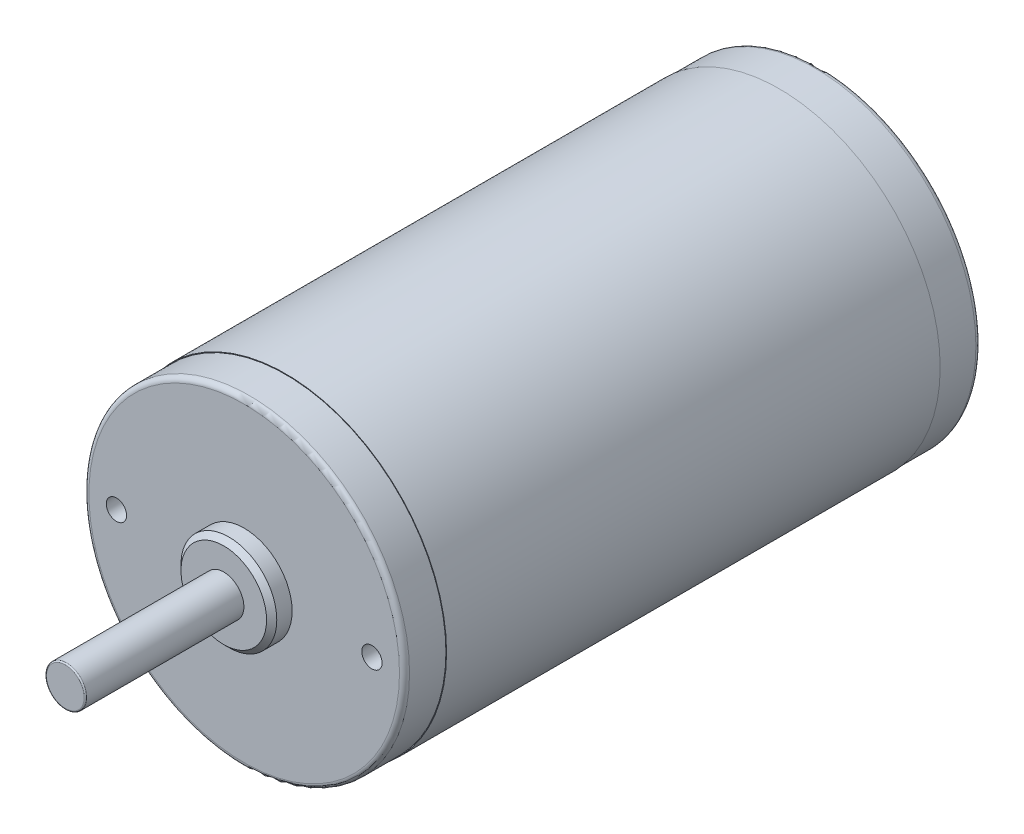
SolidWorks part; units mm, degrees
ref_plane "Front Plane" through (0, 0, 0) normal (0, 0, 1) x (1, 0, 0)
ref_plane "Top Plane" through (0, 0, 0) normal (0, 1, 0) x (1, 0, 0)
ref_plane "Right Plane" through (0, 0, 0) normal (1, 0, 0) x (0, 0, -1)
ref_plane "Plane1" through (0, 109.2962, 0) normal (0, -1, 0) x (1, 0, 0)
sketch "Sketch1" plane through (0, 109.2962, 0) normal (0, -1, 0) x (1, 0, 0)
  line L0 (67.564, 10.8204) -> (35.56, 10.8204)
  line L1 (35.56, 10.8204) -> (35.56, -87.3252)
  line L2 (35.56, -87.3252) -> (67.564, -87.3252)
  line L3 (67.564, -87.3252) -> (67.564, 10.8204)
  line L4 (35.56, 10.8204) -> (35.56, -87.3252) construction
revolve "Revolve1" add sketch "Sketch1" angle 360 about L4 reverse direction yes
sketch "Sketch2" plane through (0, 0, 10.8204) normal (0, 0, 1) x (1, 0, 0)
  circle A0 centre (35.56, 109.2962) radius 31.877
extrude "Boss-Extrude1" add sketch "Sketch2" along normal blind 8.2296
ref_plane "Plane2" through (0, 0, 18.542) normal (0, 0, -1) x (-1, 0, 0)
sketch "Sketch5" plane through (0, 0, 18.542) normal (0, 0, -1) x (-1, 0, 0)
  circle A0 centre (-35.56, 109.2962) radius 9.525
extrude "Boss-Extrude2" add sketch "Sketch5" against normal blind 4.572
sketch "Sketch6" plane through (0, 0, 23.114) normal (0, 0, 1) x (1, 0, 0)
  circle A0 centre (35.56, 109.2962) radius 4
extrude "Boss-Extrude3" add sketch "Sketch6" along normal blind 31.5
sketch "Sketch8" plane through (0, 0, -87.3252) normal (0, 0, -1) x (-1, 0, 0)
  circle A0 centre (-35.56, 109.2962) radius 31.877
extrude "Boss-Extrude4" add sketch "Sketch8" along normal blind 8.2296
sketch "Sketch9" plane through (0, 0, -95.5548) normal (0, 0, -1) x (-1, 0, 0)
  circle A0 centre (-35.56, 109.2962) radius 15.0368
extrude "Boss-Extrude5" add sketch "Sketch9" along normal blind 4.7625
ref_plane "Plane3" [suppressed] through (0, 120.5036, 0) normal (0, 1, 0) x (-1, 0, 0)
ref_plane "Plane4" [suppressed] through (0, 127.9033, 0) normal (0, 1, 0) x (-1, 0, 0)
hole_wizard "Hole2" positions "Sketch13" profile "Sketch12" legacy
sketch "Sketch13" plane through (0, 0, 19.05) normal (0, 0, 1) x (1, 0, 0)
  point P0 (60.96, 109.2962)
sketch "Sketch12" plane through (60.96, 109.2962, 19.05) normal (1, 0, 0) x (0, -1, 0)
  line L0 (0, 0) -> (0, 14.8277)
  line L1 (0, 14.8277) -> (2.0193, 13.6144)
  line L2 (2.0193, 13.6144) -> (2.0193, 0)
  line L4 (2.0193, 0) -> (0, 0)
  line L6 (0, 14.8277) -> (-2.0193, 13.6144) construction
  line L7 (0, -4.2442) -> (0, 117.3081) construction
  dimension "Diameter" = 4.0386
  dimension "Depth" = 13.6144
  dimension "Drill Angle" = 118
hole_wizard "Hole3" positions "Sketch15" profile "Sketch14" legacy
sketch "Sketch15" plane through (0, 0, 19.05) normal (0, 0, 1) x (1, 0, 0)
  point P0 (10.16, 109.2962)
sketch "Sketch14" plane through (10.16, 109.2962, 19.05) normal (1, 0, 0) x (0, -1, 0)
  line L0 (0, 0) -> (0, 14.8277)
  line L1 (0, 14.8277) -> (2.0193, 13.6144)
  line L2 (2.0193, 13.6144) -> (2.0193, 0)
  line L4 (2.0193, 0) -> (0, 0)
  line L6 (0, 14.8277) -> (-2.0193, 13.6144) construction
  line L7 (0, -4.2442) -> (0, 117.3081) construction
  dimension "Diameter" = 4.0386
  dimension "Depth" = 13.6144
  dimension "Drill Angle" = 118
chamfer "Chamfer1" distance 1.016 angle 45 1 edges at (45.085, 109.2962, 23.114) first distance on face at (45.085, 109.2962, 23.114)
fillet "Fillet1" radius 0.254 1 edges at (39.56, 109.2962, 54.614) tangent propagation no
fillet "Fillet2" radius 1 1 edges at (3.683, 109.2962, -95.5548) tangent propagation no
fillet "Fillet3" radius 1 1 edges at (67.437, 109.2962, 19.05) tangent propagation no
fillet "Fillet4" radius 1 1 edges at (20.5232, 109.2962, -100.3173) tangent propagation no
ref_plane "Plane5" [suppressed] through (39.56, 0, 0) normal (1, 0, 0) x (0, 0, -1)
